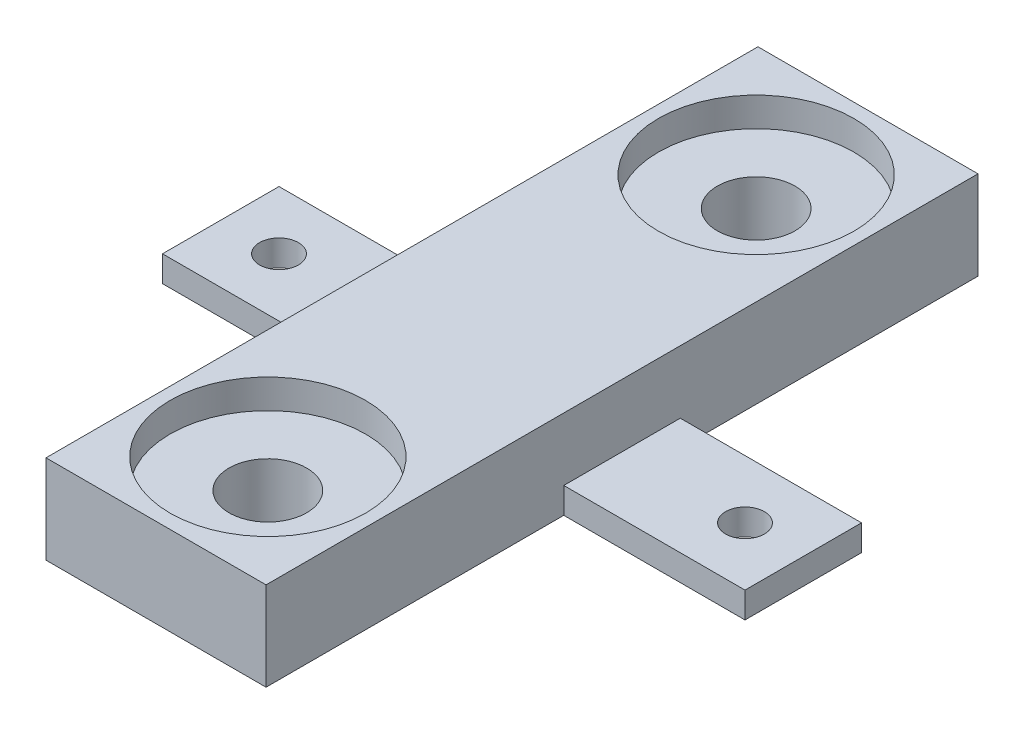
SolidWorks part; units mm, degrees
material "Nylon 101"
ref_plane "Front Plane" through (0, 0, 0) normal (0, 0, 1) x (1, 0, 0)
ref_plane "Top Plane" through (0, 0, 0) normal (0, 1, 0) x (1, 0, 0)
ref_plane "Right Plane" through (0, 0, 0) normal (1, 0, 0) x (0, 0, -1)
sketch "Sketch1" plane through (0, 0, 0) normal (0, 1, 0) x (1, 0, 0)
  line L0 (0, -18.8625) -> (0, -27.5) construction
  line L1 (-8.5, 27.5) -> (8.5, 27.5)
  line L2 (-8.5, 27.5) -> (-8.5, -27.5)
  line L3 (-8.5, -27.5) -> (8.5, -27.5)
  line L4 (8.5, 27.5) -> (8.5, -27.5)
  line L5 (-8.5, 0) -> (0, 0) construction
  line L6 (0, 18.8625) -> (0, -18.8625) construction
  line L7 (-18, 0) -> (18, 0) construction
  line L8 (-8.5, 4.5) -> (-22.5, 4.5)
  line L9 (-8.5, 4.5) -> (-8.5, -4.5)
  line L10 (-8.5, -4.5) -> (-22.5, -4.5)
  line L11 (-22.5, 4.5) -> (-22.5, -4.5)
  line L12 (8.5, 4.5) -> (22.5, 4.5)
  line L13 (8.5, 4.5) -> (8.5, -4.5)
  line L14 (8.5, -4.5) -> (22.5, -4.5)
  line L15 (22.5, 4.5) -> (22.5, -4.5)
  circle A0 centre (0, 18.8625) radius 7.55
  circle A1 centre (0, -18.8625) radius 7.55
  circle A2 centre (-18, 0) radius 1.5
  circle A3 centre (18, 0) radius 1.5
  point P24 (0, 0)
  point P26 (0, 0)
  point P28 (-22.5, 0)
  dimension "D3" = 15.1
  dimension "D7" = 3
  dimension "D1" = 55
  dimension "D2" = 17
  dimension "D4" = 37.725
  dimension "D6" = 36
  dimension "D8" = 4.5
  dimension "D9" = 9
extrude "Boss-Extrude1" add sketch "Sketch1" along normal blind 2 contours L4 L1 L2 L3 A1 A0 | L15 L12 L4 L14 A3 | L8 L11 L10 L2 A2 | A1 | A0 region at (0, 0, 0) region at (-15.3514, 0, 0) region at (15.3514, 0, 0) region at (0, 0, -18.8625) region at (0, 0, 18.8625)
extrude "Boss-Extrude2" add sketch "Sketch1<4>" along normal blind 2.6 from surface contours L4 L1 L2 L3 A1 A0 | A1 | A0 region at (0, 0, 0) region at (0, 0, -18.8625) region at (0, 0, 18.8625) starting at face at (0, 2, 0)
sketch "Sketch1<4>" plane through (0, 0, 0) normal (0, 1, 0) x (1, 0, 0) same geometry as "Sketch1"
extrude "Boss-Extrude3" add sketch "Sketch1<5>" along normal blind 2.25 from surface contours L4 L1 L2 L3 A1 A0 region at (0, 0, 0) starting at face at (0, 4.6, 0)
sketch "Sketch1<5>" plane through (0, 0, 0) normal (0, 1, 0) x (1, 0, 0) same geometry as "Sketch1"
sketch "Sketch3" plane through (0, 0, 0) normal (0, -1, 0) x (1, 0, 0)
  circle A0 centre (0, -18.8625) radius 3
  circle A1 centre (0, 18.8625) radius 3
  circle A2 centre (0, 18.8625) radius 7.55 construction
  dimension "D1" = 6
extrude "Cut-Extrude1" cut sketch "Sketch3" against normal through all
equation "\"D1@Boss-Extrude2\"= \"base_thickness\" - 2.25mm - 1.5mm"
equation "\"bottomThickness\"= .220in"
equation "\"wallThickness\"= .125in"
equation "\"wall_thickness\" = 0.125in"
equation "\"base_thickness\" = 0.25in"
